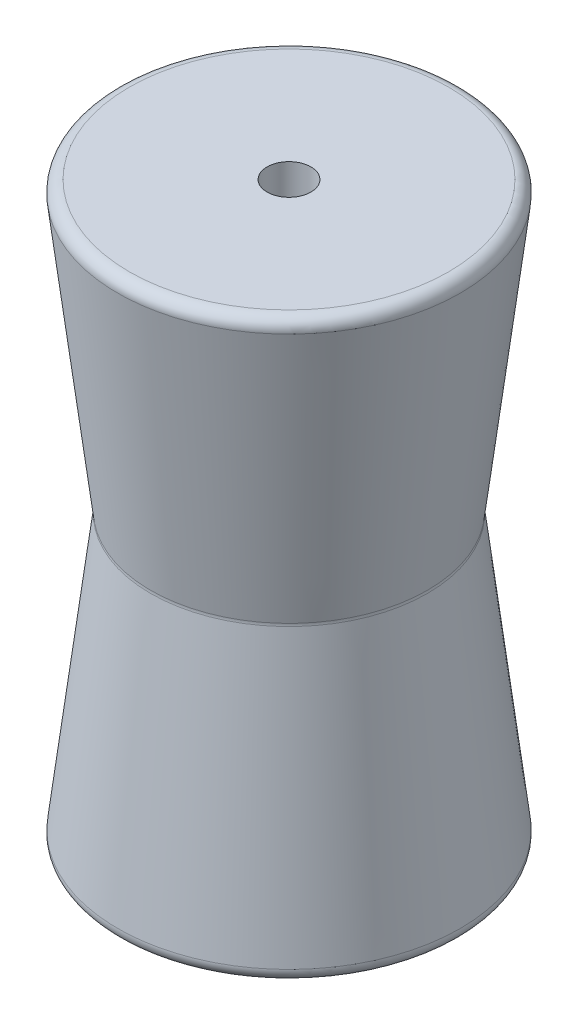
SolidWorks part; units mm, degrees
ref_plane "前视基准面" through (0, 0, 0) normal (0, 0, 1) x (1, 0, 0)
ref_plane "上视基准面" through (0, 0, 0) normal (0, 1, 0) x (1, 0, 0)
ref_plane "右视基准面" through (0, 0, 0) normal (1, 0, 0) x (0, 0, -1)
other "Configuration Table"
sketch "草图2" plane through (0, 0, 0) normal (0, 0, 1) x (1, 0, 0)
  line L0 (0, 0) -> (0, 50)
  line L1 (0, 25) -> (-12, 25) construction
  line L2 (-12, 25) -> (-15, 0)
  line L3 (-15, 0) -> (0, 0)
  line L4 (-12, 25) -> (-15, 50)
  line L5 (-15, 50) -> (0, 50)
  dimension "D1" = 15
  dimension "D2" = 12
  dimension "D3" = 25
revolve "旋转1" add sketch "草图2" angle 360 about L0 region at (-6.7778, 12.037, 0)
sketch "草图3" plane through (0, 0, 0) normal (0, -1, 0) x (1, 0, 0)
  circle A0 centre (0, 0) radius 1.9
  dimension "D1" = 3.8
extrude "切除-拉伸1" cut sketch "草图3" against normal blind 60
fillet "圆角1" radius 1 3 edges at (15, 0, 0) (12, 25, 0) (15, 50, 0)
